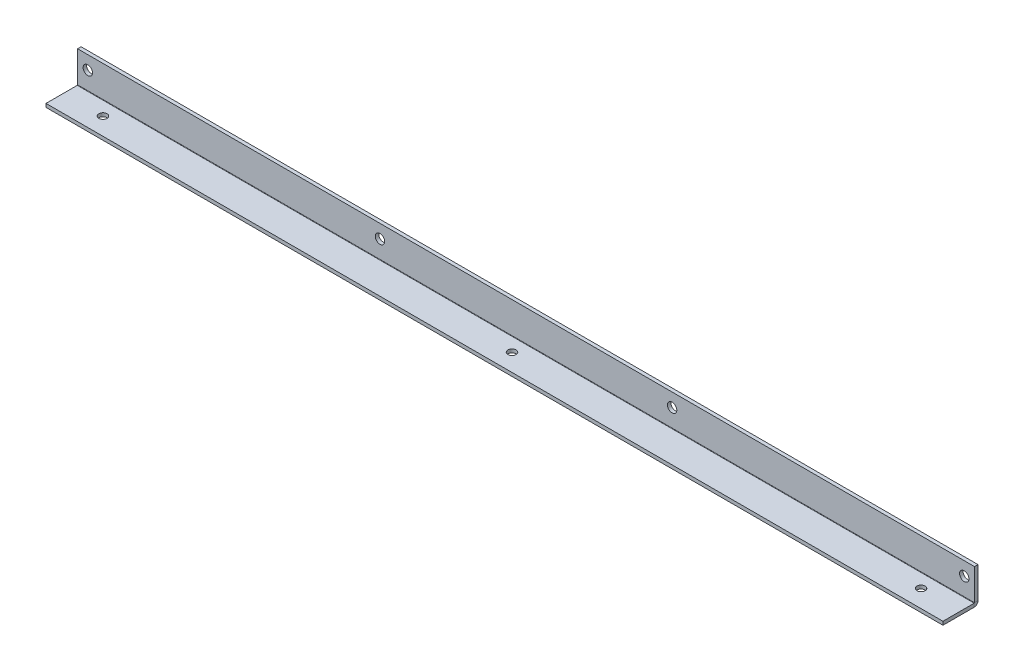
SolidWorks part; units mm, degrees
note: The reader was unsure of these and kept them because the rebuilt part matched: flange length of "Edge-Flange1".
ref_plane "Front Plane" through (0, 0, 0) normal (0, 0, 1) x (1, 0, 0)
ref_plane "Top Plane" through (0, 0, 0) normal (0, 1, 0) x (1, 0, 0)
ref_plane "Right Plane" through (0, 0, 0) normal (1, 0, 0) x (0, 0, -1)
sketch "Sketch1" plane through (0, 0, 0) normal (0, 0, 1) x (1, 0, 0)
  line L1 (0, 0) -> (389.89, 0)
  line L2 (0, 0) -> (0, 15.24)
  line L3 (0, 15.24) -> (389.89, 15.24)
  line L4 (389.89, 0) -> (389.89, 15.24)
  dimension "D1" = 389.89
  dimension "D2" = 15.24
base flange "Base-Flange1" sketch "Sketch1" thickness 1.524 reverse thickness direction no parameters "D1"=0.1524
edge flange "Edge-Flange1" sketch "Sketch8" flange angle 90 flange length 15.24 flange position material inside bend radius 0.1524 thickness 1.524 relief rectangular parameters "D6"=10
sketch "Sketch8" plane through (0, 0, 0) normal (0, -1, 0) x (1, 0, 0)
  line L0 (0, 0) -> (389.89, 0) construction
  line L1 (0, 0) -> (389.89, 0)
  line L2 (0, 0) -> (0, 13.716)
  line L3 (0, 13.716) -> (389.89, 13.716)
  line L4 (389.89, 13.716) -> (389.89, 0)
bend "EdgeBend1" bend radius 0.1524 bend angle 90 parameters "D5"=1
sketch "Sketch9" plane through (0, 0, 0) normal (0, 0, 1) x (1, 0, 0)
  line L0 (0, 15.24) -> (0, 1.6764) construction
  line L1 (389.89, 15.24) -> (0, 15.24) construction
  circle A0 centre (4.445, 9.398) radius 2.032
  circle A1 centre (131.445, 9.398) radius 2.032
  circle A2 centre (258.445, 9.398) radius 2.032
  circle A3 centre (385.445, 9.398) radius 2.032
  dimension "D1" = 4.064
  dimension "D2" = 4.445
  dimension "D3" = 5.842
  dimension "D5" = 127
  dimension "D4" = 4
extrude "Cut-Extrude1" cut sketch "Sketch9" against normal blind 2.54
sketch "Sketch10" plane through (0, 1.524, 0) normal (0, 1, 0) x (1, 0, 0)
  line L0 (389.89, -0.1524) -> (389.89, -13.716) construction
  line L1 (389.89, -13.716) -> (0, -13.716) construction
  circle A0 centre (372.745, -6.096) radius 1.778
  circle A1 centre (194.945, -6.096) radius 1.778
  circle A2 centre (17.145, -6.096) radius 1.778
  dimension "D1" = 3.556
  dimension "D2" = 17.145
  dimension "D3" = 7.62
  dimension "D5" = 177.8
  dimension "D4" = 3
extrude "Cut-Extrude2" cut sketch "Sketch10" against normal blind 2.54
sketch "Bend-Lines1" [suppressed] plane through (0, 0, 0) normal (0, 1, 0) x (1, 0, 0)
sketch "Bounding-Box1" [suppressed] plane through (0, 0, 0) normal (0, 1, 0) x (1, 0, 0)
sheet metal parameters "Sheet-Metal1" thickness 1.524 parameters "D1"=0.1524
flat pattern "Flat-Pattern1" [suppressed]
sketch "Bend-Lines2" plane through (0, 0, 0) normal (0, 1, 0) x (1, 0, 0)
sketch3d "Bounding-Box2" [suppressed]
  line L0 (0, 0, 0) -> (-393.7, 0, 0) construction
  line L1 (0, 12.7, 0) -> (-393.7, 12.7, 0) construction
  line L2 (0, 0, 0) -> (0, 12.7, 0) construction
  line L3 (-393.7, 0, 0) -> (-393.7, 12.7, 0) construction
sheet metal parameters "Sheet-Metal2" thickness 1.524 parameters "D1"=0.1524
flat pattern "Flat-Pattern1"
sketch "Bend-Lines2" plane through (0, 0, 0) normal (0, 0, 1) x (1, 0, 0)
  line L0 (0, 0.9582) -> (393.7, 0.9582) construction
  line L1 (0, 0.9582) -> (393.7, 0.9582) construction
sketch3d "Bounding-Box2" [suppressed]
  line L0 (0, -10.7835, 0) -> (393.7, -10.7835, 0) construction
  line L1 (0, 12.7, 0) -> (393.7, 12.7, 0) construction
  line L2 (0, -10.7835, 0) -> (0, 12.7, 0) construction
  line L3 (393.7, -10.7835, 0) -> (393.7, 12.7, 0) construction
bend of the flat pattern "Flatten-<EdgeBend1>1"
sheet metal parameters "Sheet-Metal3" thickness 1.524 parameters "D1"=0.1524
flat pattern "Flat-Pattern1"
sketch "Bend-Lines2" plane through (0, 0, 0) normal (0, 0, 1) x (1, 0, 0)
  line L0 (0, 0.9582) -> (393.7, 0.9582) construction
  line L1 (0, 0.9582) -> (393.7, 0.9582) construction
sketch3d "Bounding-Box2" [suppressed]
  line L0 (0, -10.7835, 0) -> (393.7, -10.7835, 0) construction
  line L1 (0, 12.7, 0) -> (393.7, 12.7, 0) construction
  line L2 (0, -10.7835, 0) -> (0, 12.7, 0) construction
  line L3 (393.7, -10.7835, 0) -> (393.7, 12.7, 0) construction
bend of the flat pattern "Flatten-<EdgeBend1>1"
sheet metal parameters "Sheet-Metal4" thickness 1.524 parameters "D1"=0.1524
flat pattern "Flat-Pattern1"
sketch "Bend-Lines2" plane through (0, 0, 0) normal (0, 0, 1) x (1, 0, 0)
  line L0 (0, 0.9582) -> (389.89, 0.9582) construction
  line L1 (0, 0.9582) -> (389.89, 0.9582) construction
sketch3d "Bounding-Box2" [suppressed]
  line L0 (0, -13.3235, 0) -> (389.89, -13.3235, 0) construction
  line L1 (0, 15.24, 0) -> (389.89, 15.24, 0) construction
  line L2 (0, -13.3235, 0) -> (0, 15.24, 0) construction
  line L3 (389.89, -13.3235, 0) -> (389.89, 15.24, 0) construction
bend of the flat pattern "Flatten-<EdgeBend1>1"
